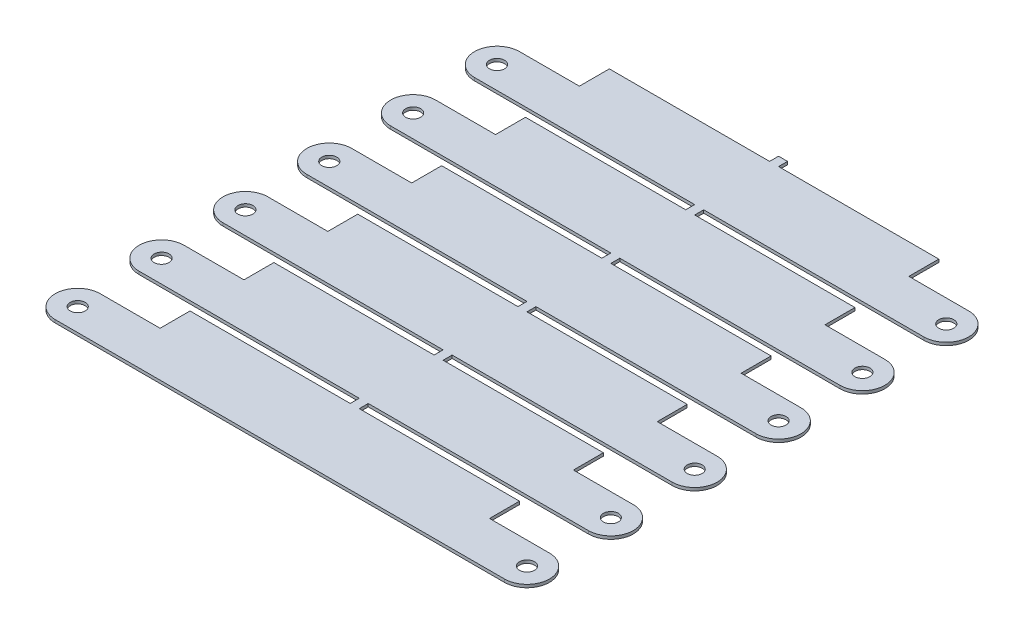
SolidWorks part; units mm, degrees
ref_plane "Front Plane" through (0, 0, 0) normal (0, 0, 1) x (1, 0, 0)
ref_plane "Top Plane" through (0, 0, 0) normal (0, 1, 0) x (1, 0, 0)
ref_plane "Right Plane" through (0, 0, 0) normal (1, 0, 0) x (0, 0, -1)
sketch "Sketch1" plane through (0, 0, 0) normal (0, 1, 0) x (1, 0, 0)
  line L0 (0, 0) -> (150, 0) construction
  line L1 (0, 7.5) -> (20, 7.5)
  line L2 (0, 7.5) -> (150, 7.5) construction
  line L3 (0, 7.5) -> (0, -7.5) construction
  line L4 (0, -7.5) -> (150, -7.5)
  line L5 (150, 7.5) -> (150, -7.5) construction
  line L6 (0, 7.5) -> (150, -7.5) construction
  line L7 (0, -7.5) -> (150, 7.5) construction
  line L8 (20, 7.5) -> (20, 17.5)
  line L9 (20, 17.5) -> (130, 17.5)
  line L10 (130, 17.5) -> (130, 7.5)
  line L11 (130, 7.5) -> (150, 7.5)
  line L12 (75, 0) -> (75, 17.5) construction
  line L13 (75, 17.5) -> (75, 20.5) construction
  line L14 (73.5, 17.5) -> (73.5, 20.5)
  line L15 (73.5, 20.5) -> (76.5, 20.5)
  line L16 (76.5, 20.5) -> (76.5, 17.5)
  circle A0 centre (0, 0) radius 2.5
  circle A1 centre (150, 0) radius 2.5
  arc A2 (0, 7.5) -> (0, -7.5) centre (0, 0) ccw
  arc A3 (150, -7.5) -> (150, 7.5) centre (150, 0) ccw
  point P5 (75, 0)
  point P19 (75, 27.0186)
  dimension "D3" = 5
  dimension "D1" = 150
  dimension "D2" = 15
  dimension "D4" = 10
  dimension "D5" = 20
  dimension "D6" = 3
  dimension "D7" = 3
extrude "Boss-Extrude1" add sketch "Sketch1" along normal blind 1 contours L4 A3 L11 L10 L9 L8 L1 A2 A0 A1 | L16 L15 L14 L9 region at (75, 0, -3.9427) region at (75, 0, -19)
pattern_linear "LPattern1" count 6 spacing 28 along (0, 0, -1) of "Boss-Extrude1"
